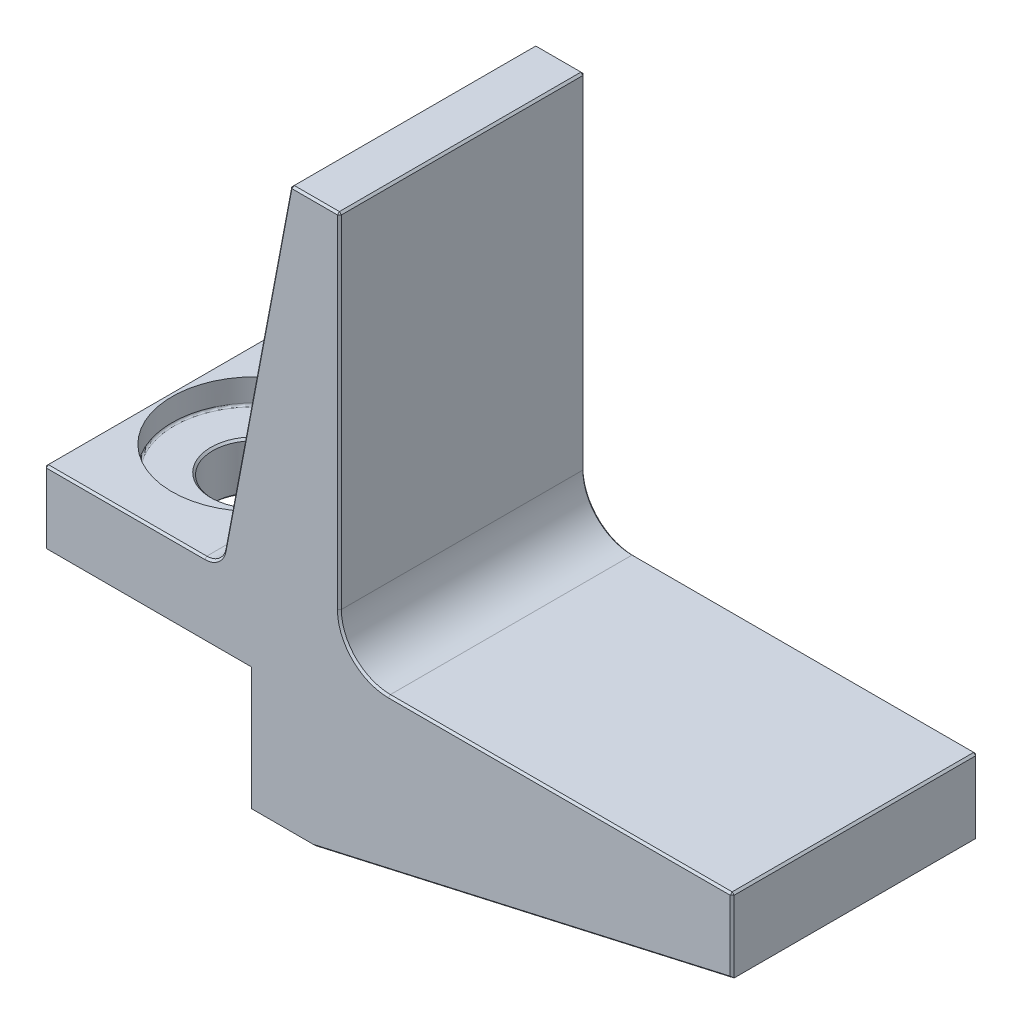
SolidWorks part; units mm, degrees
other "Markup1"
sketch "Sketch7" plane through (-38.1608, 50.8, 31.75) normal (-0.1424, 0.1459, 0.979) x (0.9898, 0.0098, 0.1425)
material "7075-T6 (SN)"
ref_plane "Front Plane" through (0, 0, 0) normal (0, 0, 1) x (1, 0, 0)
ref_plane "Top Plane" through (0, 0, 0) normal (0, 1, 0) x (1, 0, 0)
ref_plane "Right Plane" through (0, 0, 0) normal (1, 0, 0) x (0, 0, -1)
sketch "Sketch1" plane through (0, 0, 0) normal (0, 0, 1) x (1, 0, 0)
  line L0 (0, 0) -> (50.8, 0)
  line L1 (50.8, 0) -> (50.8, -9.525)
  line L2 (-11.6178, -5.8961) -> (-38.1608, -5.8961)
  line L3 (-38.1608, -5.8961) -> (-38.1608, 3.6289)
  line L4 (-38.1608, 3.6289) -> (-15.3008, 3.6289)
  line L5 (-15.3008, 3.6289) -> (-6.35, 50.8)
  line L6 (-6.35, 50.8) -> (0, 50.8)
  line L7 (0, 50.8) -> (0, 0)
  line L8 (-11.6178, -5.8961) -> (-11.6178, -21.7711)
  line L9 (-11.6178, -21.7711) -> (-3.3628, -21.7711)
  line L10 (-3.3628, -21.7711) -> (50.8, -9.525)
  dimension "D1" = 50.8
  dimension "D2" = 50.8
  dimension "D3" = 9.525
  dimension "D4" = 38.1608
  dimension "D5" = 6.35
  dimension "D6" = 22.86
  dimension "D7" = 26.543
  dimension "D8" = 9.525
  dimension "D9" = 15.875
  dimension "D10" = 8.255
  dimension "D11" = 3.6289
extrude "Boss-Extrude1" add sketch "Sketch1" along normal blind 31.75
hole_wizard "CBORE for 3/8 Binding Head Machine Screw1" positions "Sketch6" profile "Sketch3" counterbore size "3/8" standard "ANSI Inch" end condition through all
sketch "Sketch6" plane through (0, 3.6289, 0) normal (0, 1, 0) x (1, 0, 0)
  line L1 (-38.1608, -31.75) -> (-38.1608, 0) construction
  point P0 (-26.8578, -15.875)
  point P8 (-38.1608, -15.875)
  dimension "D1" = 11.303
sketch "Sketch3" plane through (-26.8578, 3.6289, 15.875) normal (1, 0, 0) x (0, 0, 1)
  line L0 (0, 0) -> (0, 25.4)
  line L1 (0, 25.4) -> (5.3975, 25.4)
  line L3 (5.3975, 25.4) -> (5.3975, 3.175)
  line L4 (10.668, 3.175) -> (5.3975, 3.175)
  line L5 (10.668, 3.175) -> (10.668, 0)
  line L7 (10.668, 0) -> (0, 0)
  line L11 (0, 0) -> (0, 107.95) construction
  dimension "Thru Hole Dia." = 10.795
  dimension "Thru Hole Depth" = 25.4
  dimension "C'Bore Depth" = 3.175
fillet "Fillet1" radius 2.54 1 edges at (-15.3008, 3.6289, 15.875)
fillet "Fillet2" radius 6.35 1 edges at (0, 0, 15.875)
chamfer "Chamfer1" distance 0.254 angle 45 31 edges at (-6.35, 50.8, 15.875) (-3.175, 50.8, 0) (-10.6293, 28.2477, 0) (-15.7842, 4.2126, 0) (-27.7825, 3.6289, 0) (-38.1608, -1.1336, 0) (-24.8893, -5.8961, 0) (50.8, -4.7625, 0) (28.575, 0, 0) (1.8599, 1.8599, 0) (0, 28.575, 0) (50.8, -4.7625, 31.75) (-24.8893, -5.8961, 31.75) (-38.1608, -5.8961, 15.875) (-38.1608, -1.1336, 31.75) (-38.1608, 3.6289, 15.875) (-27.7825, 3.6289, 31.75) (-15.7842, 4.2126, 31.75) (-10.6293, 28.2477, 31.75) (-3.175, 50.8, 31.75) (0, 50.8, 15.875) (0, 28.575, 31.75) (1.8599, 1.8599, 31.75) (28.575, 0, 31.75) (50.8, 0, 15.875) (-11.6178, -13.8336, 0) (-7.4903, -21.7711, 0) (23.7186, -15.6481, 0) (23.7186, -15.6481, 31.75) (-7.4903, -21.7711, 31.75) (-11.6178, -13.8336, 31.75) first distance on face at (-3.175, 50.8, 15.875) first distance on face at (-12.0656, 20.6784, 15.7047) first distance on face at (-15.9703, 4.4374, 5.4659) first distance on face at (-27.6767, 3.6289, 15.875) first distance on face at (-38.1608, -1.1336, 15.875) first distance on face at (-32.2553, -5.8961, 15.875) first distance on face at (50.8, -4.7625, 15.875) first distance on face at (-2.6597, 4.1753, 0) first distance on face at (2.5174, 2.5174, 15.875) first distance on face at (0, 28.575, 15.875) first distance on face at (-15.9703, 4.4374, 26.2841) first distance on face at (-2.6597, 4.1753, 31.75) first distance on face at (-11.6178, -13.8336, 15.875) first distance on face at (-7.4903, -21.7711, 15.875) first distance on face at (23.7186, -15.6481, 15.875)
fillet "Fillet3" radius 0.254 1 edges at (-26.8578, 0.4539, 26.543)
chamfer "Chamfer2" distance 0.254 angle 45 1 edges at (-32.2553, -5.8961, 15.875)
chamfer "Chamfer3" distance 0.254 angle 45 1 edges at (-26.8578, 0.4539, 21.2725)
